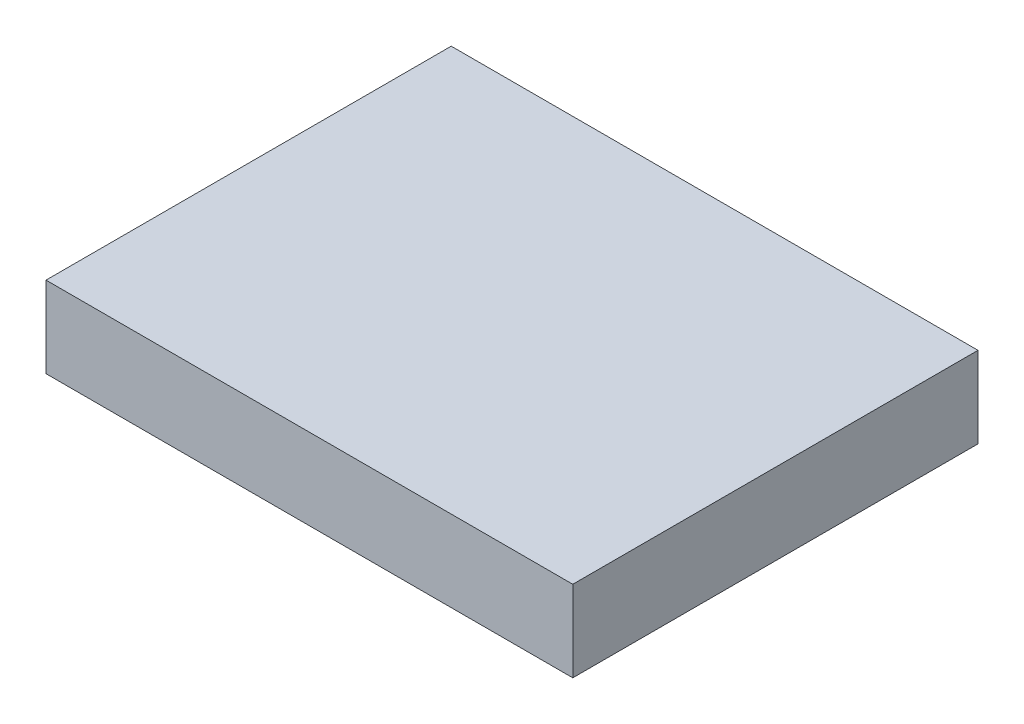
SolidWorks part; units mm, degrees
ref_plane "Plano frontal" through (0, 0, 0) normal (0, 0, 1) x (1, 0, 0)
ref_plane "Plano superior" through (0, 0, 0) normal (0, 1, 0) x (1, 0, 0)
ref_plane "Plano direito" through (0, 0, 0) normal (1, 0, 0) x (0, 0, -1)
sketch "Esboço1" plane through (0, 0, 0) normal (0, 1, 0) x (1, 0, 0)
  line L1 (-49.8055, 50) -> (80.1945, 50)
  line L2 (-49.8055, 50) -> (-49.8055, -50)
  line L3 (-49.8055, -50) -> (80.1945, -50)
  line L4 (80.1945, 50) -> (80.1945, -50)
  line L5 (-49.8055, 50) -> (80.1945, -50) construction
  line L6 (-49.8055, -50) -> (80.1945, 50) construction
  point P6 (0, 0)
  dimension "D1" = 100
  dimension "D2" = 130
extrude "Ressalto-extrusão1" add sketch "Esboço1" along normal blind 10 and the other way blind 10
